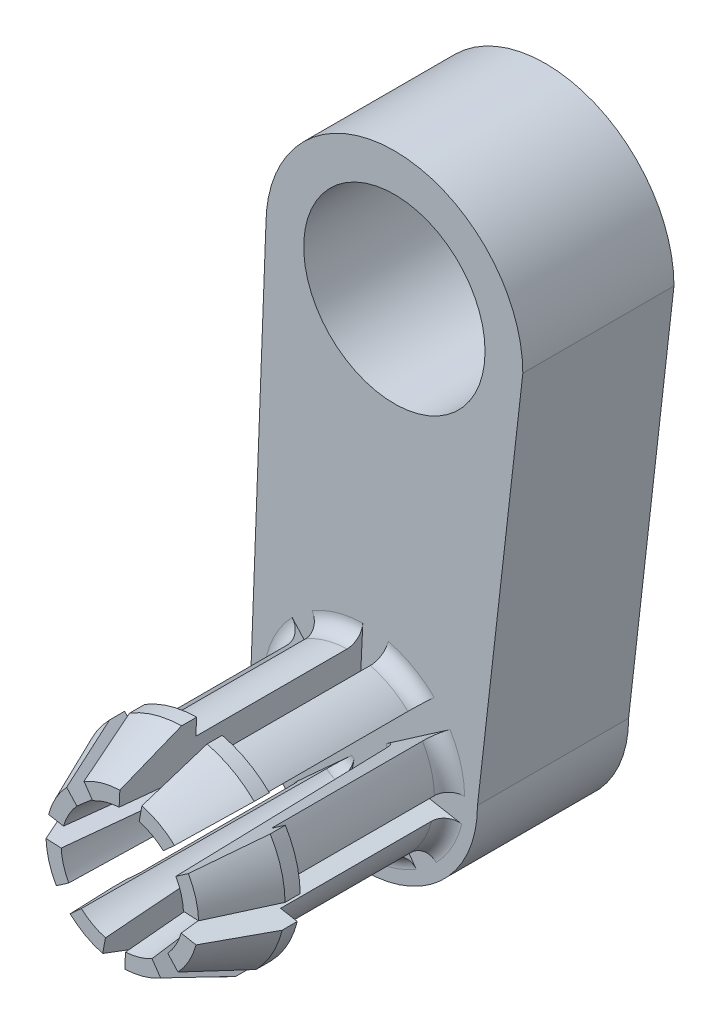
SolidWorks part; units mm, degrees
ref_plane "Front Plane" through (0, 0, 0) normal (0, 0, 1) x (1, 0, 0)
ref_plane "Top Plane" through (0, 0, 0) normal (0, 1, 0) x (1, 0, 0)
ref_plane "Right Plane" through (0, 0, 0) normal (1, 0, 0) x (0, 0, -1)
sketch "Sketch1" plane through (0, 0, 0) normal (0, 0, 1) x (1, 0, 0)
  line L1 (0, 0) -> (15.5, 0) construction
  line L2 (0, 0) -> (0, 7.5) construction
  line L6 (1, 33.769) -> (0, 7.5)
  line L7 (18, 33.769) -> (15, 7.5)
  arc A0 (0, 7.5) -> (15, 7.5) centre (7.5, 7.5) ccw
  arc A2 (17.7811, 31.8525) -> (1, 33.769) centre (9.5, 33.769) ccw
  circle A3 centre (9.5, 33.769) radius 6
  point P2 (1, 33.769)
  point P8 (18, 33.769)
  point P14 (15.5, 33.769)
  dimension "D1" = 15
  dimension "D2" = 12
  dimension "D5" = 17
  dimension "D3" = 26.345
  dimension "D4" = 2
extrude "Boss-Extrude1" add sketch "Sketch1" along normal blind 10 contours A0 region at (8.3444, 18.8425, 0)
sketch "Sketch3" plane through (0, 0, 10) normal (0, 0, 1) x (1, 0, 0)
  circle A0 centre (7.5, 7.5) radius 7.5
  arc A1 (0, 7.5) -> (15, 7.5) centre (7.5, 7.5) ccw construction
  point P6 (7.5, 7.5)
ref_plane "Plane1" through (6.5579, -0.7489, 0) normal (0.9935, -0.1135, 0) x (0, 0, -1)
sketch "Sketch7" plane through (6.5579, -0.7489, 0) normal (0.9935, -0.1135, 0) x (0, 0, -1)
  line L0 (-10, 8.3026) -> (-28.1597, 8.3026) construction
  line L2 (-10, 2.6526) -> (-21, 2.6526)
  line L3 (-10, 15.8026) -> (-10, 0.8026) construction
  line L4 (-21, 2.6526) -> (-21, 1.5326)
  line L5 (-21, 1.5326) -> (-22, 1.5326)
  line L6 (-22, 1.5326) -> (-26, 3.2526)
  line L7 (-26, 3.2526) -> (-26, 4.2526)
  line L8 (-26, 4.2526) -> (-10, 5.8526)
  line L9 (-10, 5.8526) -> (-10, 2.6526)
  dimension "D1" = 11
  dimension "D2" = 1.12
  dimension "D3" = 1
  dimension "D4" = 4
  dimension "D5" = 1
  dimension "D6" = 1.6
  dimension "D7" = 3.2
  dimension "D8" = 5.65
revolve "Revolve1" add sketch "Sketch7" angle 360 about L0
sketch "Sketch8" plane through (0, 0, 10) normal (0, 0, 1) x (1, 0, 0)
  line L0 (15.6607, 13.285) -> (13.0715, -9.387) construction
  line L1 (18, 33.769) -> (15, 7.5) construction
  line L2 (7.5, 7.5) -> (27.1219, 5.2591) construction
  line L3 (7.5454, 7.8974) -> (15.0056, 7.5487)
  line L4 (4.0286, -22.8968) -> (9.0873, 21.3989) construction
  line L5 (7.4546, 7.1026) -> (14.8013, 5.7603)
  line L6 (15.0056, 7.5487) -> (14.8013, 5.7603)
  line L7 (7.5454, 7.8974) -> (7.4546, 7.1026)
  dimension "D1" = 1.8
  dimension "D2" = 0.8
extrude "Cut-Extrude1" cut sketch "Sketch8" along normal through all
ref_axis "Axis1" through (7.5, 7.5, 26) along (0, 0, -1)
pattern_circular "CirPattern1" count 8 over 360 about axis through (7.5, 7.5, 26) along (0, 0, -1) of "Cut-Extrude1"
fillet "Fillet1" radius 1 16 edges at (9.6425, 6.3117, 10) (9.8553, 8.1747, 10) (8.1747, 5.1447, 10) (6.3117, 5.3575, 10) (5.1447, 6.8253, 10) (5.3575, 8.6883, 10) (6.8253, 9.8553, 10) (8.6883, 9.6425, 10) (12.9315, 9.0559, 10) (10.2405, 12.4409, 10) (5.9441, 12.9315, 10) (2.5591, 10.2405, 10) (2.0685, 5.9441, 10) (4.7595, 2.5591, 10) (9.0559, 2.0685, 10) (12.4409, 4.7595, 10)
sketch "Sketch10" plane through (0, 0, 10) normal (0, 0, 1) x (1, 0, 0)
  line L2 (15, 7.5) -> (18, 33.769)
  line L3 (1, 33.769) -> (0, 7.5)
  line L4 (15, 7.5) -> (18, 33.769)
  line L5 (1, 33.769) -> (0, 7.5)
  circle A0 centre (9.5, 33.769) radius 8.5
  circle A1 centre (7.5, 7.5) radius 7.5
  arc A2 (0, 7.5) -> (15, 7.5) centre (7.5, 7.5) ccw
  arc A3 (18, 33.769) -> (1, 33.769) centre (9.5, 33.769) ccw
  arc A4 (0, 7.5) -> (15, 7.5) centre (7.5, 7.5) ccw
  arc A5 (18, 33.769) -> (1, 33.769) centre (9.5, 33.769) ccw
  line M38 (15, 7.5) -> (18, 33.769)
  line M40 (1, 33.769) -> (0, 7.5)
  dimension "D1" = 0
extrude "Cut-Extrude2" [suppressed] cut sketch "Sketch10" against normal through all both and the other way through all contours A1 A0 M38 M40
sketch "Sketch9" plane through (0, 0, 10) normal (0, 0, 1) x (1, 0, 0)
  line L0 (17.4541, 36.766) -> (27.107, 11.1476)
  line L1 (3.5578, 27.6912) -> (9.3424, 22.0355)
  line L2 (9.5, 33.769) -> (7.5, 7.5) construction
  line L3 (24.7743, 5.9941) -> (10.1445, 0.4817)
  line L5 (5.4773, 14.7221) -> (7.6249, 15.3236)
  circle A0 centre (9.5, 33.769) radius 8.5
  arc A1 (18, 33.769) -> (1, 33.769) centre (9.5, 33.769) ccw construction
  circle A3 centre (7.5, 7.5) radius 7.5 construction
  arc A5 (24.7743, 5.9941) -> (27.107, 11.1476) centre (23.3639, 9.7372) ccw
  arc A6 (7.6249, 15.3236) -> (9.3424, 22.0355) centre (6.5461, 19.1754) ccw
  arc A7 (10.1445, 0.4817) -> (5.4773, 14.7221) centre (7.5, 7.5) ccw
  arc M42 (0, 7.5) -> (15, 7.5) centre (7.5, 7.5) ccw
  dimension "D5" = 4
  dimension "20" = 25
  dimension "D2" = 90
  dimension "D3" = 50
  dimension "D4" = 60
extrude "Boss-Extrude2" [suppressed] add sketch "Sketch9" against normal up to surface (10 mm away) contours A0 L2 L3 A5 L0 M42 | L2 A0 L1 A6 L5 A7 | L2 A6 L5 A7 up to face at (15.5, 33.769, 0)
